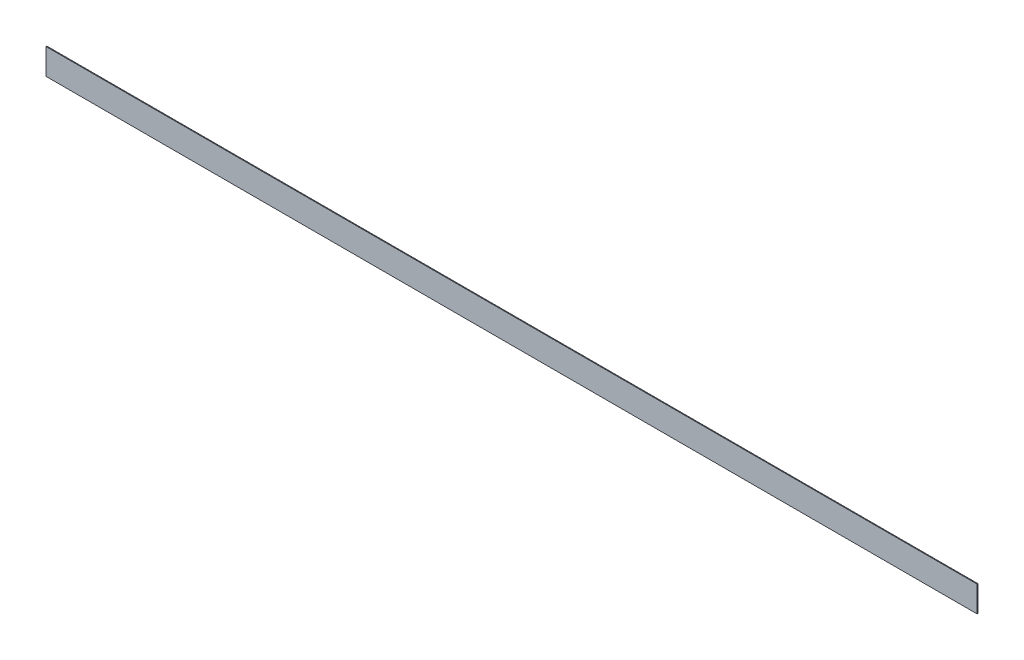
SolidWorks part; units mm, degrees
ref_plane "Front Plane" through (0, 0, 0) normal (0, 0, 1) x (1, 0, 0)
ref_plane "Top Plane" through (0, 0, 0) normal (0, 1, 0) x (1, 0, 0)
ref_plane "Right Plane" through (0, 0, 0) normal (1, 0, 0) x (0, 0, -1)
sketch "Sketch1" plane through (0, 0, 0) normal (0, 0, 1) x (1, 0, 0)
  line L1 (0, 0) -> (1828.8, 0)
  line L2 (0, 0) -> (0, 50.8)
  line L3 (0, 50.8) -> (1828.8, 50.8)
  line L4 (1828.8, 0) -> (1828.8, 50.8)
  dimension "D1" = 50.8
  dimension "D2" = 1828.8
extrude "Boss-Extrude1" add sketch "Sketch1" along normal blind 1.5875
